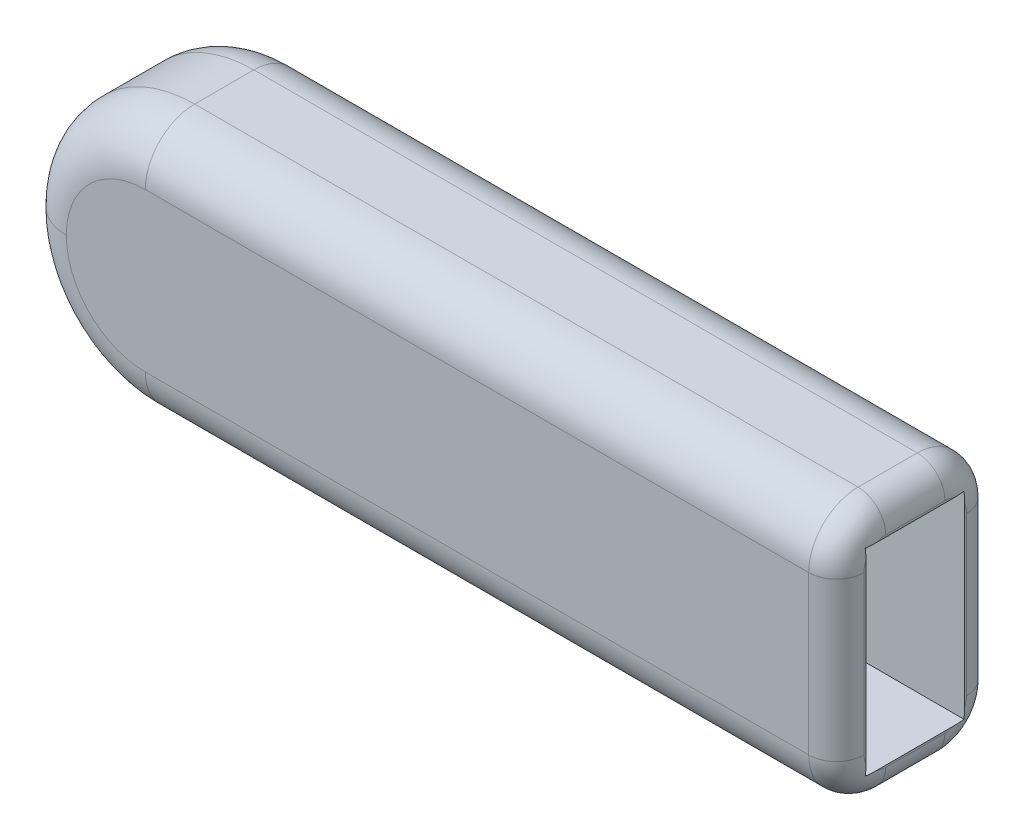
SolidWorks part; units mm, degrees
ref_plane "Plane1" through (0, 0, 0) normal (0, 0, 1) x (1, 0, 0)
ref_plane "Plane2" through (0, 0, 0) normal (0, 1, 0) x (-1, 0, 0)
ref_plane "Plane3" through (0, 0, 0) normal (1, 0, 0) x (0, 0, -1)
sketch "Sketch1" plane through (0, 0, 0) normal (0, 0, 1) x (1, 0, 0)
  line L0 (0, 0) -> (50.8, 0)
  line L1 (0, 0) -> (0, 12.7)
  line L2 (50.8, 12.7) -> (0, 12.7)
  line L3 (50.8, 12.7) -> (50.8, 0)
  dimension "D1" = 12.7
  dimension "D2" = 50.8
extrude "Base-Extrude" add sketch "Sketch1" along normal blind 6.35
fillet "Fillet1" radius 6.35 2 edges at (0, 12.7, 3.175) (0, 0, 3.175)
shell "Shell1" thickness 1.905 removed face at (50.8, 6.35, 3.175) outward yes
fillet "Fillet3" radius 3.175 8 edges at (28.575, 14.605, 8.255) (28.575, -1.905, 8.255) (28.575, 14.605, -1.905) (28.575, -1.905, -1.905) (0.5128, 0.5128, 8.255) (0.5128, 12.1872, 8.255) (0.5128, 0.5128, -1.905) (0.5128, 12.1872, -1.905)
fillet "Fillet4" radius 1.778 8 edges at (50.8, 13.6751, 7.3251) (50.8, 6.35, -1.905) (50.8, -0.9751, -0.9751) (50.8, 13.6751, -0.9751) (50.8, -1.905, 3.175) (50.8, 14.605, 3.175) (50.8, -0.9751, 7.3251) (50.8, 6.35, 8.255)
